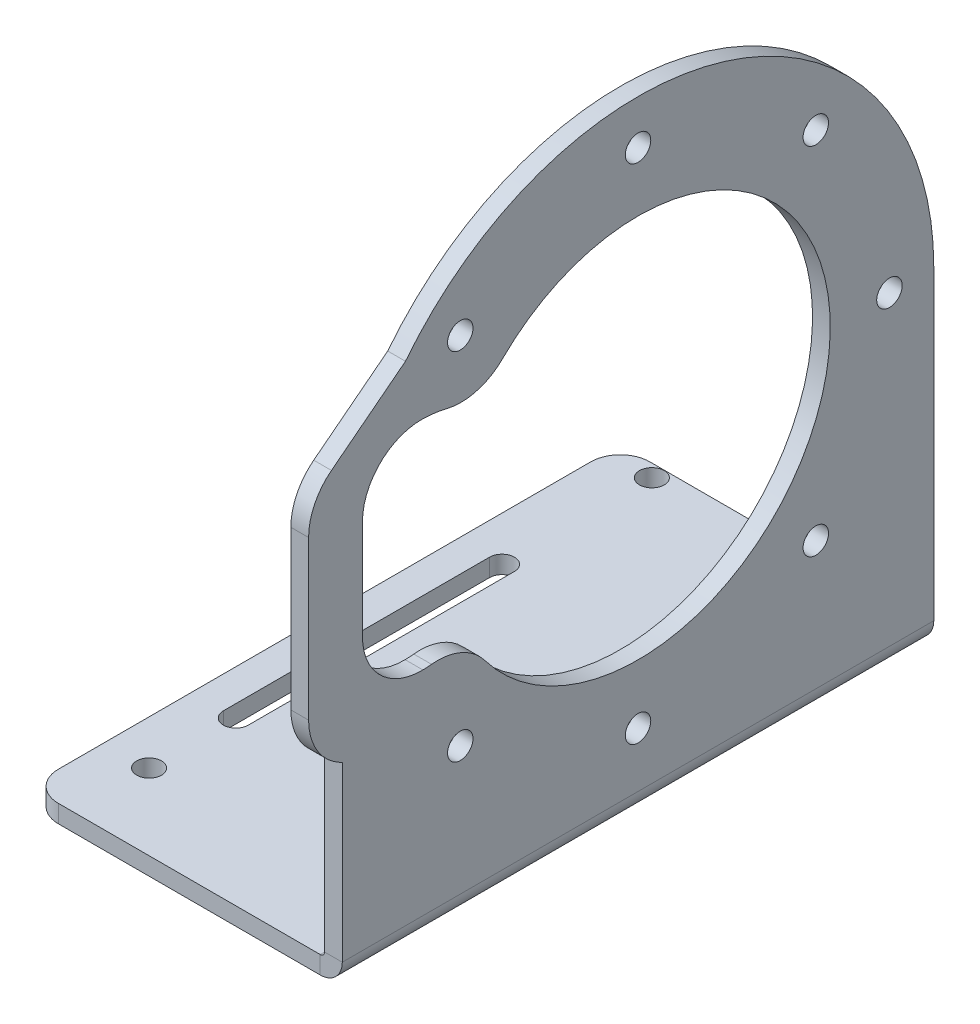
SolidWorks part; units mm, degrees
note: The reader was unsure of these and kept them because the rebuilt part matched: flange length of "边线-法兰1".
material "冷轧钢板 08F"
ref_plane "前视基准面" through (0, 0, 0) normal (0, 0, 1) x (1, 0, 0)
ref_plane "上视基准面" through (0, 0, 0) normal (0, 1, 0) x (1, 0, 0)
ref_plane "右视基准面" through (0, 0, 0) normal (1, 0, 0) x (0, 0, -1)
sketch "草图1" plane through (0, 0, 0) normal (1, 0, 0) x (0, 0, -1)
  line L0 (-50, -22.5108) -> (-50, -55.5)
  line L1 (-50, -55.5) -> (50, -55.5)
  line L2 (50, -55.5) -> (50, 0)
  line L4 (-46.5956, 10.9978) -> (-46.5956, -5.7774)
  line L7 (-55.695, 13.2651) -> (-55.695, -13.4711)
  line L9 (-39.3204, 30.8854) -> (-51.8319, 21.1606)
  arc A0 (-39.2988, -16.1819) -> (-36.775, 21.3037) centre (0, 0) ccw construction
  circle A1 centre (0, 42.5) radius 2.15
  circle A2 centre (30.052, 30.052) radius 2.15
  circle A3 centre (42.5, 0) radius 2.15
  circle A4 centre (30.052, -30.052) radius 2.15
  circle A5 centre (0, -42.5) radius 2.15
  circle A6 centre (-30.052, -30.052) radius 2.15
  circle A8 centre (-30.052, 30.052) radius 2.15
  arc A9 (50, 0) -> (-39.3204, 30.8854) centre (0, 0) ccw
  arc A10 (-25.9232, -19.602) -> (-22.8947, 23.067) centre (0, 0) ccw
  arc A11 (-42.4532, -2.1495) -> (-42.4532, 2.1495) centre (-42.5, 0) ccw [skipped]
  arc A12 (-50.5456, -22.2159) -> (-50, -22.5108) centre (-36.775, 2.6102) ccw
  arc A14 (-32.347, 20.4587) -> (-36.3818, 20.9956) centre (-36.775, 2.6102) ccw
  arc A15 (-36.3818, -15.7751) -> (-34.9124, -15.6847) centre (-36.775, 2.6102) ccw
  arc A16 (-46.5956, -5.7774) -> (-36.3818, -15.7751) centre (-36.5956, -5.7774) ccw
  arc A17 (-46.5956, 10.9978) -> (-36.3818, 20.9956) centre (-36.5956, 10.9978) cw
  arc A18 (-55.695, -13.4711) -> (-50.5456, -22.2159) centre (-45.695, -13.4711) ccw
  arc A19 (-51.8319, 21.1606) -> (-55.695, 13.2651) centre (-45.695, 13.2651) ccw
  arc A20 (-34.9124, -15.6847) -> (-25.9232, -19.602) centre (-33.8996, -25.6333) cw
  arc A21 (-32.347, 20.4587) -> (-22.8947, 23.067) centre (-29.9392, 30.1645) ccw
  point P35 (-46.5956, -12.9375)
  dimension "D1" = 85
  dimension "D2" = 4.3
  dimension "D4" = 100
  dimension "D5" = 65
  dimension "D6" = 13
  dimension "D7" = 10
  dimension "D8" = 10
  dimension "D9" = 10
  dimension "D3" = 8
base flange "基体-法兰1" sketch "草图1" thickness 3 reverse thickness direction no parameters "D1"=0.7366
edge flange "边线-法兰1" sketch "草图8" flange angle 90 flange length 50 flange position material inside bend radius 0.7366 thickness 3 relief rectangular parameters "D6"=10
sketch "草图8" plane through (-3, -55.5, 0) normal (0, -1, 0) x (0, 0, 1)
  line L2 (-50, 0) -> (-50, 50)
  line L3 (-50, 50) -> (50, 50)
  line L4 (50, 50) -> (50, 0)
  line L7 (50, 0) -> (-50, 0) construction
  line L8 (50, 0) -> (-50, 0)
bend "边线折弯1" bend radius 0.7366 bend angle 90 parameters "D5"=1
sketch "草图9" plane through (0, -52.5, 0) normal (0, 1, 0) x (1, 0, 0)
  line L0 (-53, 5.3398) -> (-3, 5.3398) construction
  line L2 (-3, 50) -> (-3, -39.3204) construction
  line L3 (-28.3683, 50) -> (-28.3683, -50) construction
  line L4 (-53, 50) -> (-3.7366, 50) construction
  line L5 (-3.7366, -50) -> (-53, -50) construction
  line L7 (-45.5, -37.1602) -> (-10.5, -37.1602) construction
  line L8 (-45.5, -37.1602) -> (-45.5, 47.8398) construction
  line L9 (-45.5, 47.8398) -> (-10.5, 47.8398) construction
  line L10 (-10.5, -37.1602) -> (-10.5, 47.8398) construction
  line L11 (-28, 47.8398) -> (-28, -37.1602) construction
  line L12 (-45.5, 5.3398) -> (-10.5, 5.3398) construction
  circle A0 centre (-45.5, 47.8398) radius 2.1
  circle A1 centre (-10.5, 47.8398) radius 2.1
  circle A2 centre (-45.5, -37.1602) radius 2.1
  circle A3 centre (-10.5, -37.1602) radius 2.1
  point P12 (-28, 5.3398)
  dimension "D3" = 4.2
  dimension "D4" = 4.2
  dimension "D5" = 4.2
  dimension "D6" = 4.2
  dimension "D1" = 85
  dimension "D2" = 35
extrude "切除-拉伸1" cut sketch "草图9" against normal blind 10 normal cut yes
fillet "圆角1" radius 5 2 edges at (-53, -54, 50) (-53, -54, -50)
sketch "草图10" plane through (0, -52.5, 0) normal (0, 1, 0) x (1, 0, 0)
  line L0 (-45.5, 22.5) -> (-45.5, -22.5) construction
  line L1 (-43.4, 22.5) -> (-43.4, -22.5)
  line L2 (-47.6, 22.5) -> (-47.6, -22.5)
  line L3 (-10.5, 22.5) -> (-10.5, -22.5) construction
  line L4 (-8.4, 22.5) -> (-8.4, -22.5)
  line L5 (-12.6, 22.5) -> (-12.6, -22.5)
  line L6 (-48, 50) -> (-3.7366, 50) construction
  arc A0 (-43.4, 22.5) -> (-47.6, 22.5) centre (-45.5, 22.5) ccw
  arc A1 (-47.6, -22.5) -> (-43.4, -22.5) centre (-45.5, -22.5) ccw
  arc A2 (-8.4, 22.5) -> (-12.6, 22.5) centre (-10.5, 22.5) ccw
  arc A3 (-12.6, -22.5) -> (-8.4, -22.5) centre (-10.5, -22.5) ccw
  circle A4 centre (-28, 0) radius 2.1
  circle A5 centre (-10.5, 47.8398) radius 2.1 construction
  point P3 (-45.5, 0)
  point P8 (-10.5, 0)
  dimension "D5" = 2.1
  dimension "D6" = 2.1
  dimension "D7" = 4.2
  dimension "D8" = 17.5
  dimension "D1" = 45
  dimension "D2" = 45
  dimension "D3" = 22.5
  dimension "D4" = 22.5
  dimension "D9" = 50
extrude "切除-拉伸2" cut sketch "草图10" against normal blind 10 normal cut yes
sketch "折弯-线1" [suppressed] plane through (0, 0, 0) normal (0, 1, 0) x (1, 0, 0)
sketch "边界框1" [suppressed] plane through (0, 0, 0) normal (0, 1, 0) x (1, 0, 0)
sheet metal parameters "钣金6" thickness 3 parameters "D1"=0.7366
flat pattern "平板型式6" [suppressed]
sketch "折弯-线2" plane through (0, 0, 0) normal (0, 1, 0) x (1, 0, 0)
sketch "边界框2" [suppressed] plane through (0, 0, 0) normal (0, 1, 0) x (1, 0, 0)
sheet metal parameters "钣金7" thickness 3 parameters "D1"=0.7366
flat pattern "平板型式6" [suppressed]
sketch "折弯-线2" plane through (0, 0, 0) normal (0, 1, 0) x (1, 0, 0)
sketch "边界框2" [suppressed] plane through (0, 0, 0) normal (0, 1, 0) x (1, 0, 0)
bend of the flat pattern "展平-<边线折弯1>1"
sheet metal parameters "钣金8" thickness 3 parameters "D1"=0.7366
flat pattern "平板型式6" [suppressed]
sketch "折弯-线2" plane through (0, 0, 0) normal (0, 1, 0) x (1, 0, 0)
sketch "边界框2" [suppressed] plane through (0, 0, 0) normal (0, 1, 0) x (1, 0, 0)
bend of the flat pattern "展平-<边线折弯1>1"
sheet metal parameters "钣金9" thickness 3 parameters "D1"=0.7366
flat pattern "平板型式6"
sketch "折弯-线2" plane through (0, 0, 0) normal (1, 0, 0) x (0, 0, -1)
  line L0 (-50, -53.52) -> (50, -53.52) construction
  line L1 (-50, -53.52) -> (50, -53.52) construction
sketch3d "边界框2" [suppressed]
  line L0 (50, -104.54, 0) -> (50, 50, 0) construction
  line L1 (-50, -104.54, 0) -> (-50, 50, 0) construction
  line L2 (50, -104.54, 0) -> (-50, -104.54, 0) construction
  line L3 (50, 50, 0) -> (-50, 50, 0) construction
bend of the flat pattern "展平-<边线折弯1>1"
